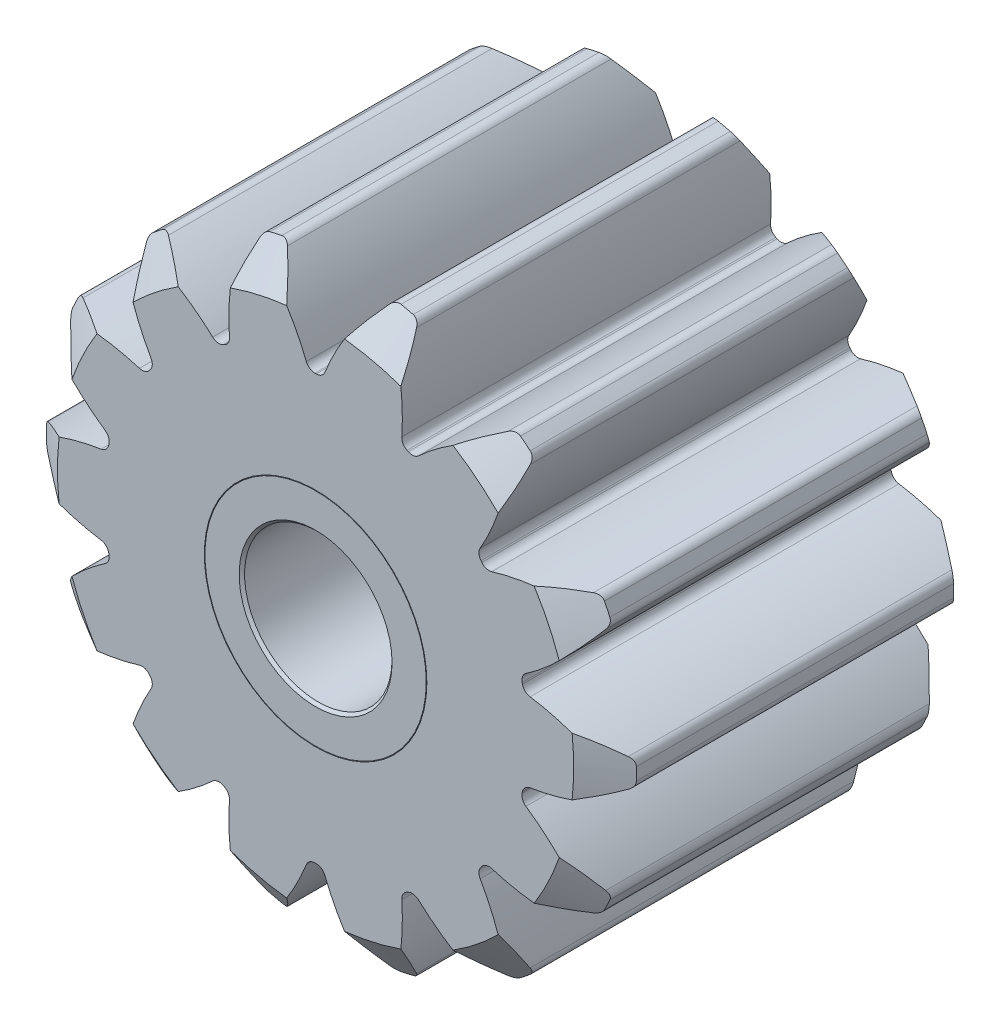
SolidWorks part; units mm, degrees
ref_plane "前视基准面" through (0, 0, 0) normal (0, 0, 1) x (1, 0, 0)
ref_plane "上视基准面" through (0, 0, 0) normal (0, 1, 0) x (1, 0, 0)
ref_plane "右视基准面" through (0, 0, 0) normal (1, 0, 0) x (0, 0, -1)
sketch "草图1" plane through (0, 0, 0) normal (1, 0, 0) x (0, 0, -1)
  line L0 (0, 0) -> (30, 0) construction
  line L1 (0, 6) -> (30, 6)
  line L4 (30, 6) -> (30, 24)
  line L5 (30, 24) -> (0, 24)
  line L6 (0, 24) -> (0, 6)
  line L7 (0, 0) -> (-3, 0) construction
  line L8 (-3, 0) -> (-3, -14) construction
  dimension "P" = 12
  dimension "B" = 30
  dimension "M" = 3
  dimension "Z" = 14
  dimension "D" = 48
sketch "草图2" plane through (0, 0, 0) normal (0, 0, 1) x (1, 0, 0)
  line L0 (0, 6) -> (0, 12) construction
  circle A0 centre (0, 0) radius 6
  circle A3 centre (0, 0) radius 9
  point P6 (0, 9)
  dimension "(D1)" = 6
sketch "草图11" plane through (-11.8785, -4, 0) normal (0, 0, 1) x (1, 0, 0)
  line L0 (11.8785, 4) -> (35.8785, 4) construction
  line L1 (32.7465, 1.6487) -> (11.8785, 4) construction
  circle A0 centre (11.8785, 4) radius 17.25
  arc A1 (28.8141, 0.7214) -> (29.1285, 4) centre (11.8785, 4) ccw construction
  arc A2 (32.7465, 1.6487) -> (32.8785, 4) centre (11.8785, 4) ccw construction
  arc A3 (35.86, 3.0578) -> (35.86, 4.9422) centre (11.8785, 4) ccw construction
  arc A4 (28.8141, 0.7214) -> (35.86, 3.0578) centre (26.3715, 19.8801) ccw construction
  point P1 (25.8785, 4)
  point P7 (11.8785, 7)
  point P13 (32.7465, 1.6487)
  point P17 (35.86, 4.9422)
  point P18 (28.8141, 7.2786)
  dimension "D1" = 48
  dimension "D" = 42
  dimension "D2" = 34.5
  dimension "m" = 3
  dimension "z" = 14
  dimension "D3" = 6.429
  dimension "D4" = 1.885
  dimension "D5" = 6.5973
extrude "拉伸-齿轮a" add sketch "草图11" against normal blind 30
sketch "草图3" plane through (-1.3611, -4, 0) normal (0, 0, 1) x (1, 0, 0)
  line L1 (1.3611, 4) -> (25.3611, 4) construction
  line L2 (18.6111, 4) -> (25.3611, 4) construction
  circle A2 centre (1.3611, 4) radius 17.25 construction
  arc A3 (18.2966, 0.7214) -> (25.3426, 3.0578) centre (15.8541, 19.8801) ccw construction
  arc A4 (25.3426, 3.0578) -> (25.3426, 4.9422) centre (1.3611, 4) ccw construction
  arc A5 (18.2966, 0.7214) -> (18.2966, 7.2786) centre (1.3611, 4) ccw
  arc A6 (18.2966, 0.7214) -> (25.3426, 3.0578) centre (15.8541, 19.8801) ccw
  arc A7 (25.3426, 3.0578) -> (25.3426, 4.9422) centre (1.3611, 4) ccw
  arc A8 (18.2966, 7.2786) -> (25.3426, 4.9422) centre (15.8541, -11.8801) cw
extrude "拉伸-齿轮b" add sketch "草图3" along normal up to surface (-30 mm away) up to face at (17.25, 0, -30)
fillet "圆角-齿轮" radius 0.75 4 edges at (23.9815, -0.9422, -15) (23.9815, 0.9422, -15) (16.9356, -3.2786, -15) (16.9356, 3.2786, -15)
pattern_circular "阵列-齿轮" count 14 over 360 about axis through (0, 0, -30) along (0, 0, 1) of "拉伸-齿轮b", "圆角-齿轮"
sketch "草图4" plane through (0, 0, -30) normal (0, 0, -1) x (-1, 0, 0)
  line L0 (-21, 0) -> (-27, 0) construction
  circle A0 centre (0, 0) radius 27
  circle A1 centre (0, 0) radius 21
extrude "切除-齿轮" cut sketch "草图4" against normal blind 3 draft 55
extrude "切除-拉伸2" cut sketch "草图4<2>" along normal blind 3 draft 55 from vertex starting at point (0, 6, 0)
sketch "草图4<2>" plane through (0, 0, -30) normal (0, 0, -1) x (-1, 0, 0) same geometry as "草图4"
sketch "草图13" plane through (0, 0, 0) normal (0, 0, 1) x (1, 0, 0)
  circle A0 centre (0, 0) radius 6
extrude "切除-拉伸4" cut sketch "草图13" against normal through all
chamfer "倒角1" distance 0.22 angle 45 2 edges at (6, 0, -30) (6, 0, 0)
sketch "草图14" plane through (0, 0, 0) normal (1, 0, 0) x (0, 0, -1)
  line L0 (0, 0) -> (30, 0) construction
  line L1 (0, 9) -> (0, -9) construction
  line L2 (37.5, 9.05) -> (22.5, 9.05)
  line L3 (37.5, 9.05) -> (37.5, 9)
  line L4 (37.5, 9) -> (22.5, 9)
  line L5 (22.5, 9.05) -> (22.5, 9)
  line L6 (7.5, 9.05) -> (-7.5, 9.05)
  line L7 (7.5, 9.05) -> (7.5, 9)
  line L8 (7.5, 9) -> (-7.5, 9)
  line L9 (-7.5, 9.05) -> (-7.5, 9)
  line L10 (30, 6) -> (30, 24) construction
  line L11 (22.5, 9) -> (7.5, 9) construction
  point P12 (0, 9)
  point P16 (30, 9)
  dimension "D1" = 0.05
revolve "金属" cut sketch "草图14" angle 360 mid plane about L0
